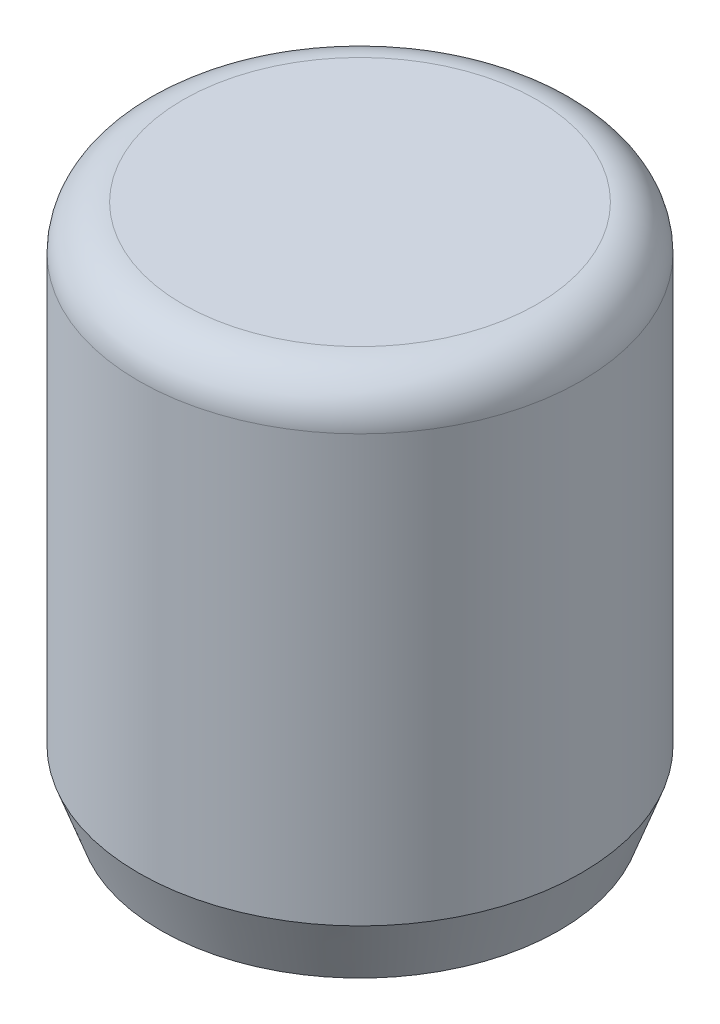
SolidWorks part; units mm, degrees
ref_plane "Спереди" through (0, 0, 0) normal (0, 0, 1) x (1, 0, 0)
ref_plane "Сверху" through (0, 0, 0) normal (0, 1, 0) x (1, 0, 0)
ref_plane "Справа" through (0, 0, 0) normal (1, 0, 0) x (0, 0, -1)
sketch "Sketch1" plane through (0, 0, 0) normal (0, 1, 0) x (1, 0, 0)
  circle A0 centre (0, 0) radius 5
  dimension "D1" = 10
extrude "Boss-Extrude1" add sketch "Sketch1" along normal blind 12
sketch "Sketch2" plane through (0, 0, 0) normal (0, -1, 0) x (1, 0, 0)
  circle A0 centre (0, 0) radius 3.3
  dimension "D1" = 6.6
extrude "Cut-Extrude1" cut sketch "Sketch2" against normal blind 6
fillet "Fillet1" radius 1 1 edges at (0, 12, 5)
chamfer "Chamfer1" distance 0.5 angle 70 1 edges at (0, 0, 5) first distance on face at (0, 0, -3.3)
